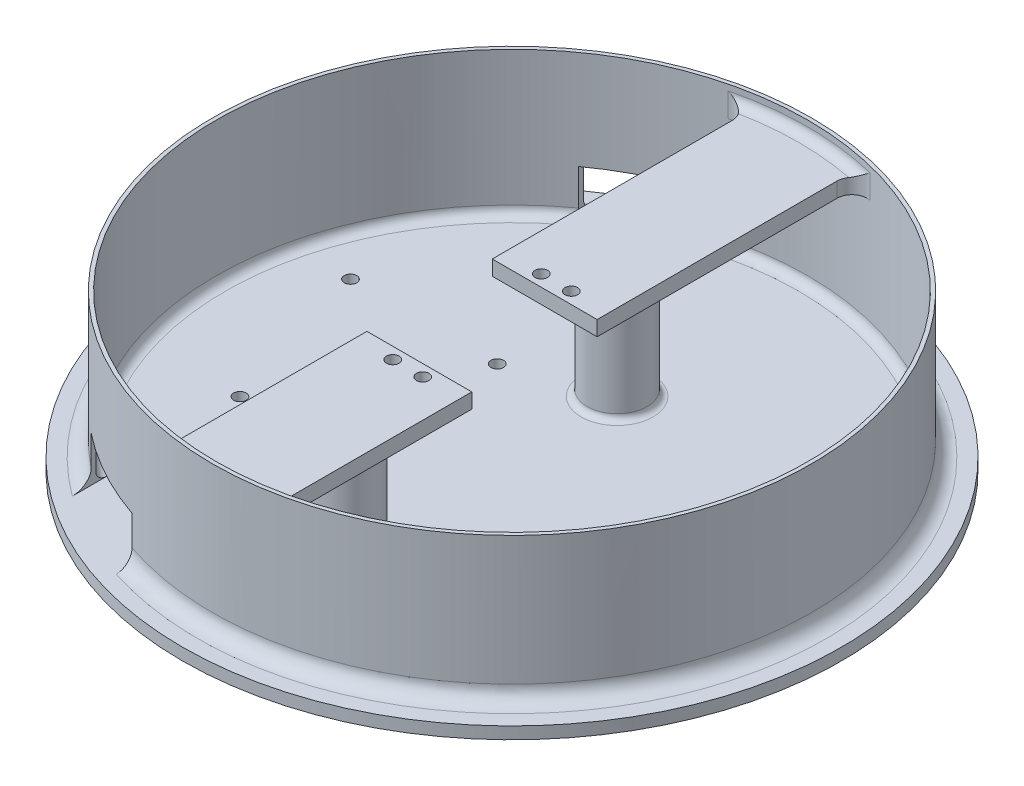
SolidWorks part; units mm, degrees
ref_plane "Front Plane" through (0, 0, 0) normal (0, 0, 1) x (1, 0, 0)
ref_plane "Top Plane" through (0, 0, 0) normal (0, 1, 0) x (1, 0, 0)
ref_plane "Right Plane" through (0, 0, 0) normal (1, 0, 0) x (0, 0, -1)
sketch "Sketch1" plane through (0, 0, 0) normal (0, 1, 0) x (1, 0, 0)
  circle A0 centre (0, 0) radius 100
  dimension "D1" = 200
extrude "Boss-Extrude1" add sketch "Sketch1" along normal blind 50
sketch "Sketch2" plane through (0, 50, 0) normal (0, 1, 0) x (1, 0, 0)
  circle A0 centre (0, 0) radius 98.75
  dimension "D1" = 197.5
extrude "Cut-Extrude1" cut sketch "Sketch2" against normal blind 48
sketch "Sketch3" plane through (0, 2, 0) normal (0, 1, 0) x (1, 0, 0)
  line L0 (-17.5, -98.4568) -> (17.5, -98.4568)
  line L7 (-17.5, 10.0818) -> (17.5, 10.0818)
  line L8 (-17.5, 10.0818) -> (-17.5, 98.858)
  line L9 (-17.5, 98.858) -> (17.5, 98.858)
  line L10 (17.5, 10.0818) -> (17.5, 98.858)
  line L11 (-17.5, 10.0818) -> (17.5, 98.858) construction
  line L12 (-17.5, 98.858) -> (17.5, 10.0818) construction
  line L13 (-17.5, -98.4568) -> (-17.5, -30.9182)
  line L14 (-17.5, -30.9182) -> (17.5, -30.9182)
  line L15 (17.5, -98.4568) -> (17.5, -30.9182)
  line L16 (-17.5, -98.4568) -> (17.5, -30.9182) construction
  line L17 (-17.5, -30.9182) -> (17.5, -98.4568) construction
  circle A0 centre (0, 0) radius 100 construction
  point P0 (0, 0)
  point P6 (0, 54.4699)
  point P11 (0, -64.6875)
  circle M2 centre (0, 0) radius 98.75
  dimension "D1" = 41
  dimension "D3" = 35
  dimension "D4" = 35
extrude "Boss-Extrude2" add sketch "Sketch3" along normal blind 5 from offset 38 contours L7 L10 L9 L8 M2 | L15 L14 L13 M2 | L7 | L14 region at (0, 2, 64.5331) region at (0, 2, -54.1575)
sketch "Sketch4" plane through (0, 2, 0) normal (0, 1, 0) x (1, 0, 0)
  line L0 (0, 0) -> (0, -30.9182) construction
  line L1 (-17.5, -30.9182) -> (17.5, -30.9182) construction
  circle A0 centre (-5, 14.8) radius 2.1
  circle A1 centre (5, 14.8) radius 2.1
  circle A2 centre (-5, -34.8) radius 2.1
  circle A3 centre (5, -34.8) radius 2.1
  dimension "D1" = 4.2
  dimension "D2" = 49.6
  dimension "D3" = 49.6
  dimension "D4" = 10
  dimension "D5" = 5
  dimension "D6" = 14.8
extrude "Cut-Extrude3" cut sketch "Sketch4" against normal blind 8 from surface contours A1 | A0 | A2 | A3 region at (-5, 2, -14.8) region at (5, 2, -14.8) region at (-5, 2, 34.8) region at (5, 2, 34.8) starting at face at (0, 45, -54.0252)
sketch "Sketch5" plane through (0, 2, 0) normal (0, 1, 0) x (1, 0, 0)
  line L0 (0, 0) -> (0, 150) construction
  line L1 (0, 0) -> (142.6585, 46.3525) construction
  line L2 (0, 0) -> (88.1678, -121.3525)
  line L3 (0, 0) -> (-142.6585, 46.3525) construction
  line L4 (0, 0) -> (-88.1678, -121.3525)
  circle A0 centre (0, 0) radius 110
  dimension "D10" = 220
  dimension "D1" = 72
  dimension "D2" = 72
  dimension "D3" = 72
  dimension "D4" = 72
  dimension "D5" = 150
  dimension "D6" = 150
  dimension "D7" = 150
  dimension "D8" = 150
  dimension "D9" = 150
extrude "Boss-Extrude4" add sketch "Sketch5" against normal blind 4 contours A0
fillet "Fillet1" radius 5 1 edges at (0, 2, 100)
sketch "Sketch6" plane through (0, 2, 0) normal (0, 1, 0) x (1, 0, 0)
  circle A0 centre (-78.3263, 24.4186) radius 2.1
  circle A1 centre (-29.3263, 24.4186) radius 2.1
  circle A2 centre (-34.8263, -27.9313) radius 2.1
  circle A3 centre (-62.8263, -27.9814) radius 2.1
  dimension "D1" = 4.2
  dimension "D2" = 4.2
  dimension "D3" = 4.2
  dimension "D4" = 52.638
  dimension "D5" = 49
  dimension "D6" = 4.2
  dimension "D7" = 28
  dimension "D8" = 54.6444
  dimension "D9" = 38.1614
extrude "Cut-Extrude4" cut sketch "Sketch6" against normal blind 10
sketch "Sketch11" plane through (0, 2, 0) normal (0, 1, 0) x (1, 0, 0)
  line L1 (-62.0234, -73.0243) -> (-32.1488, -73.0243)
  line L2 (-62.0234, -73.0243) -> (-62.0234, -105.1972)
  line L3 (-62.0234, -105.1972) -> (-32.1488, -105.1972)
  line L4 (-32.1488, -73.0243) -> (-32.1488, -105.1972)
  line L5 (-57.8083, 104.0104) -> (-28.3026, 104.0104)
  line L6 (-57.8083, 104.0104) -> (-57.8083, 76.378)
  line L7 (-57.8083, 76.378) -> (-28.3026, 76.378)
  line L8 (-28.3026, 104.0104) -> (-28.3026, 76.378)
  circle A0 centre (0, 0) radius 110 construction
extrude "Cut-Extrude7" cut sketch "Sketch11" along normal blind 15
fillet "Fillet2" radius 3 1 edges at (0, 45, -98.75)
fillet "Fillet3" radius 5 2 edges at (-17.5, 44, -97.187) (17.5, 44, -97.187)
sketch "Sketch13" plane through (0, 2, 0) normal (0, 1, 0) x (1, 0, 0)
  line L0 (-17.5, 10.0818) -> (17.5, 10.0818) construction
  line L1 (-17.5, -30.9182) -> (17.5, -30.9182) construction
  circle A0 centre (0, -55.9182) radius 10
  circle A1 centre (0, 35.0818) radius 10
  dimension "D1" = 20
  dimension "D2" = 25
  dimension "D3" = 25
extrude "Boss-Extrude8" add sketch "Sketch13" along normal blind 40
fillet "Fillet4" radius 2 2 edges at (0, 2, 65.9182) (0, 2, -25.0818)
fillet "Fillet6" radius 3 1 edges at (98.7293, 2, 2.0201)
fillet "Fillet8" radius 3 1 edges at (-98.7144, 2, -2.6519)
sketch "Sketch14" plane through (0, 45, 0) normal (0, 1, 0) x (1, 0, 0)
  line L0 (17.5, 10.0818) -> (17.5, 91.01) construction
  line L1 (-17.5, 10.0818) -> (17.5, 10.0818)
  line L2 (-17.5, 10.0818) -> (-17.5, 10.92)
  line L3 (-17.5, 10.92) -> (17.5, 10.92)
  line L4 (17.5, 10.0818) -> (17.5, 10.92)
  circle A0 centre (-5, 14.8) radius 2.1 construction
  dimension "D1" = 3.88
extrude "Cut-Extrude8" cut sketch "Sketch14" against normal up to surface (43 mm away) up to face at (0, 2, 67.9182)
